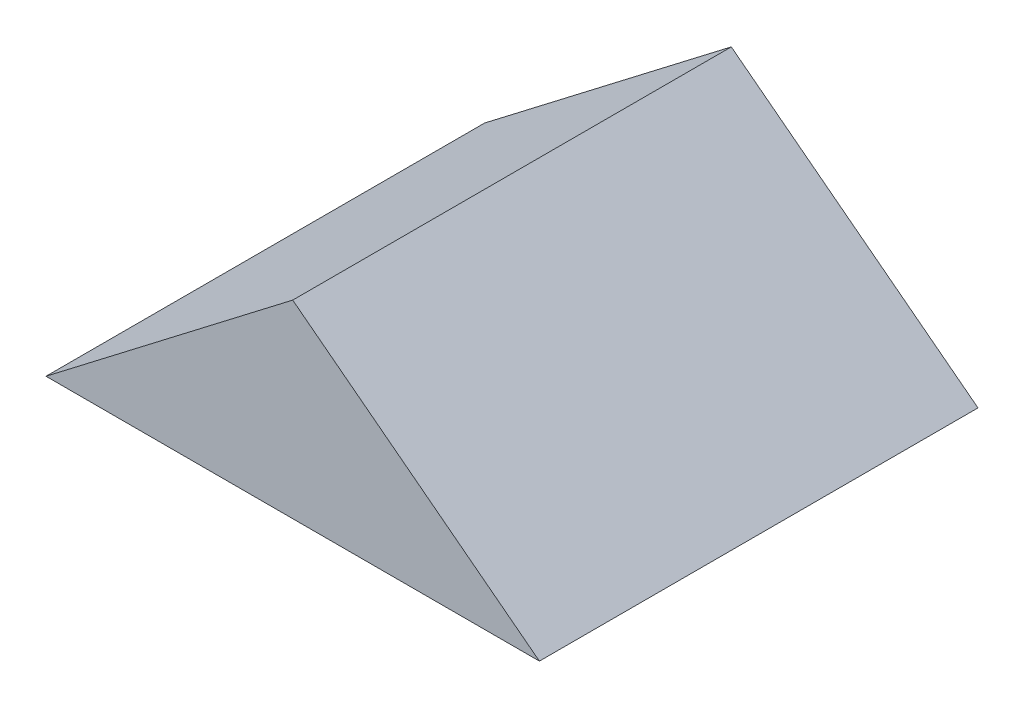
SolidWorks part; units mm, degrees
ref_plane "Front Plane" through (0, 0, 0) normal (0, 0, 1) x (1, 0, 0)
ref_plane "Top Plane" through (0, 0, 0) normal (0, 1, 0) x (1, 0, 0)
ref_plane "Right Plane" through (0, 0, 0) normal (1, 0, 0) x (0, 0, -1)
sketch "Sketch1" plane through (0, 0, 0) normal (0, 0, 1) x (1, 0, 0)
  line L0 (0, 0) -> (0, 61.3862) construction
  line L1 (0, 61.3862) -> (-80, 0)
  line L2 (-80, 0) -> (80, 0) construction
  line L3 (80, 0) -> (0, 61.3862)
  line L4 (80, 0) -> (90, -7.6733)
  line L5 (90, -7.6733) -> (-90, -7.6733)
  line L6 (-90, -7.6733) -> (-80, 0)
  line L8 (-80, -0.1733) -> (80, -0.1733) construction
  line L9 (-80, -0.1733) -> (-80, -7.6733) construction
  line L10 (-80, -7.6733) -> (80, -7.6733)
  line L11 (80, -0.1733) -> (80, -7.6733) construction
  point P3 (0, 0)
  dimension "D1" = 105
  dimension "D2" = 160
  dimension "D3" = 10
  dimension "D4" = 7.5
extrude "Boss-Extrude1" add sketch "Sketch1" along normal blind 160 contours L3 L1 L6 L5 L4
sketch "Sketch2" plane through (0, -7.6733, 0) normal (0, -1, 0) x (1, 0, 0)
  line L8 (-80, 10) -> (80, 10)
  line L9 (80, 10) -> (80, 150)
  line L10 (80, 150) -> (-80, 150)
  line L11 (-80, 150) -> (-80, 10)
  line L12 (-80, 10) -> (80, 10)
  line L13 (80, 10) -> (80, 150)
  line L14 (80, 150) -> (-80, 150)
  line L15 (-80, 150) -> (-80, 10)
  dimension "D1" = 10
extrude "Cut-Extrude1" cut sketch "Sketch2" against normal blind 5
shell "Shell1" thickness 7.5 removed face at (0, -2.6733, 80)
sketch "Sketch4" plane through (0, -2.6733, 0) normal (0, -1, 0) x (1, 0, 0)
  line L0 (-1.006, 150) -> (-1.006, 98.2663)
  line L1 (80, 150) -> (-80, 150) construction
  line L2 (-1.006, 98.2663) -> (80, 98.2663)
  line L3 (80, 10) -> (80, 150) construction
  line L4 (-1.006, 162.1195) -> (87.4327, 162.1195)
rib "Rib1" [suppressed] sketch "Sketch4" sketch "Sketch4" thickness 10 extrusion direction normal to sketch draft on no parameters "D1"=10
sketch "Sketch5" [suppressed] plane through (0, -2.6733, 0) normal (0, -1, 0) x (1, 0, 0)
  line L0 (3.994, 103.2663) -> (3.994, 157.1195) construction
  line L1 (3.994, 157.1195) -> (-6.006, 157.1195)
  line L2 (3.994, 157.1195) -> (3.994, 103.2663)
  line L3 (3.994, 103.2663) -> (-6.006, 103.2663)
  line L4 (-6.006, 157.1195) -> (-6.006, 103.2663)
  line L5 (-6.006, 93.2663) -> (-6.006, 182.5) construction
extrude "Cut-Extrude2" [suppressed] cut sketch "Sketch5" against normal blind 19.05
